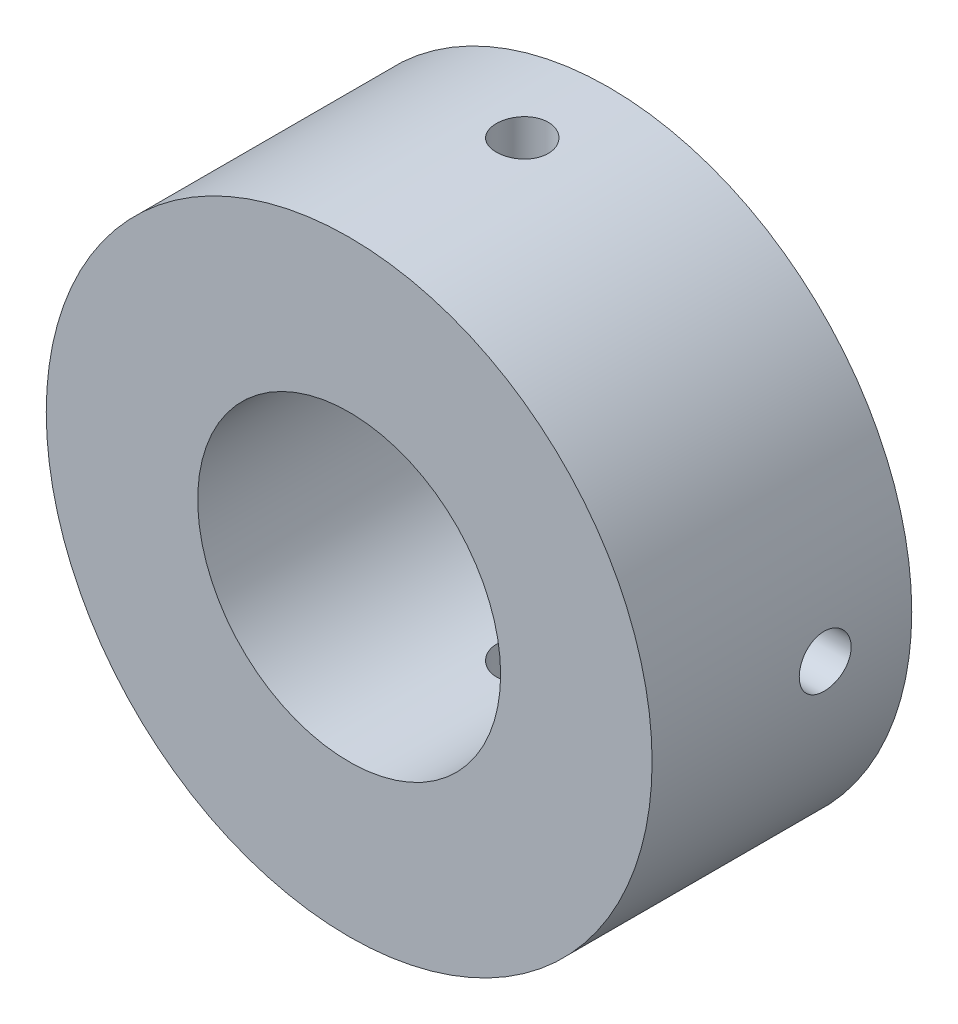
SolidWorks part; units mm, degrees
ref_plane "Front Plane" through (0, 0, 0) normal (0, 0, 1) x (1, 0, 0)
ref_plane "Top Plane" through (0, 0, 0) normal (0, 1, 0) x (1, 0, 0)
ref_plane "Right Plane" through (0, 0, 0) normal (1, 0, 0) x (0, 0, -1)
ref_axis "Z" through (0, 0, 10.75) along (0, 0, -1)
ref_axis "X" through (17.0818, 0, 0) along (-1, 0, 0)
ref_axis "Y" through (0, 15.4, 0) along (0, -1, 0)
sketch "Sketch1" plane through (0, 0, 0) normal (0, 0, 1) x (1, 0, 0)
  circle A0 centre (0, 0) radius 17.5
  circle A1 centre (0, 0) radius 8.75
  dimension "D1" = 35
  dimension "D2" = 17.5
extrude "Boss-Extrude1" add sketch "Sketch1" against normal blind 5 and the other way blind 10
sketch "Sketch2" plane through (0, 0, 0) normal (0, 1, 0) x (1, 0, 0)
  line L0 (-15.4, 0) -> (15.4, 0) construction
  line L1 (0, -8.25) -> (0, 8.25) construction
  circle A0 centre (0, 0) radius 1.5
  dimension "D1" = 3
extrude "Cut-Extrude1" cut sketch "Sketch2" against normal through all both and the other way through all
sketch "Sketch3" plane through (0, 0, 0) normal (1, 0, 0) x (0, 0, -1)
  circle A0 centre (0, 0) radius 1.5
  dimension "D1" = 3
extrude "Cut-Extrude2" cut sketch "Sketch3" along normal through all
equation "\"EyeDiameter\" = 35"
equation "\"BasePlaneDistance\" = 30"
equation "\"EyeClearance\" = 2"
equation "\"EyeOD\"= \"EyeDiameter\""
equation "\"D1@Sketch1\"=\"EyeOD\""
equation "\"D2@Sketch1\"=\"EyeDiameter\"*0.5"
equation "\"pinHoleDiameter\"= 3"
equation "\"D1@Sketch2\"=\"pinHoleDiameter\""
equation "\"D1@Sketch3\"=\"pinHoleDiameter\""
